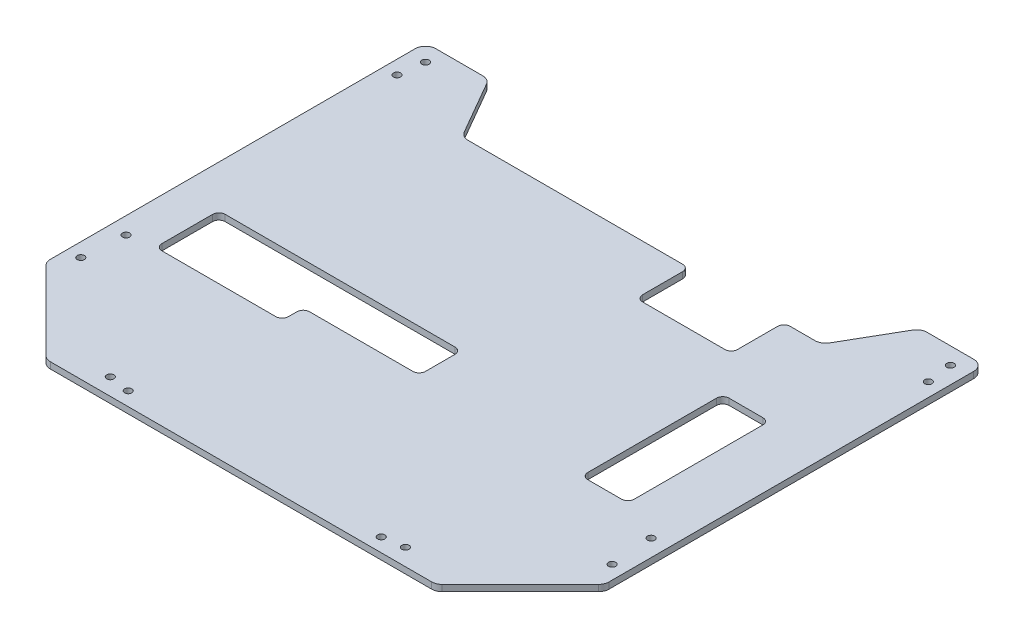
SolidWorks part; units mm, degrees
material "Acier non allié"
ref_plane "Front" through (0, 0, 0) normal (0, 0, 1) x (1, 0, 0)
ref_plane "Top" through (0, 0, 0) normal (0, 1, 0) x (1, 0, 0)
ref_plane "Right" through (0, 0, 0) normal (1, 0, 0) x (0, 0, -1)
sketch "Esquisse1" plane through (0, 0, 0) normal (0, 1, 0) x (1, 0, 0)
  line L0 (0, 0) -> (0, 1919.0564) construction
  line L1 (-92.5, 0) -> (92.5, 0)
  line L2 (92.5, 0) -> (132.5, 40)
  line L3 (132.5, 40) -> (132.5, 220)
  line L4 (132.5, 220) -> (102.5, 220)
  line L5 (102.5, 220) -> (85.1795, 190)
  line L6 (85.1795, 190) -> (-85.1795, 190)
  line L7 (-102.5, 220) -> (-85.1795, 190)
  line L8 (-132.5, 220) -> (-102.5, 220)
  line L9 (-132.5, 40) -> (-132.5, 220)
  line L10 (-92.5, 0) -> (-132.5, 40)
  point P12 (0, 190)
  dimension "D1" = 132.5
  dimension "D2" = 220
  dimension "D3" = 30
  dimension "D4" = 30
  dimension "D5" = 40
  dimension "D6" = 40
  dimension "D7" = 60
extrude "Boss.-Extru.1" add sketch "Esquisse1" along normal blind 3
fillet "Congé1" radius 5 10 edges at (132.5, 1.5, -220) (102.5, 1.5, -220) (85.1795, 1.5, -190) (-85.1795, 1.5, -190) (-102.5, 1.5, -220) (-132.5, 1.5, -220) (-132.5, 1.5, -40) (-92.5, 1.5, 0) (92.5, 1.5, 0) (132.5, 1.5, -40)
sketch "Esquisse2" plane through (0, 0, 0) normal (0, -1, 0) x (1, 0, 0)
  line L0 (0, 0) -> (0, -330.9968) construction
  line L1 (-90.4289, 0) -> (90.4289, 0) construction
  line L2 (-105.3868, -220) -> (-127.5, -220) construction
  line L3 (-132.5, -215) -> (-132.5, -42.0711) construction
  line L4 (-90.4289, 0) -> (90.4289, 0) construction
  line L5 (132.5, -42.0711) -> (132.5, -215) construction
  line L6 (127.5, -220) -> (105.3868, -220) construction
  circle A0 centre (-70, -8) radius 1
  circle A1 centre (-124.5, -70) radius 1
  circle A2 centre (-124.5, -212) radius 1
  circle A3 centre (124.5, -212) radius 1
  circle A4 centre (124.5, -70) radius 1
  circle A5 centre (70, -8) radius 1
  circle A6 centre (126, -50) radius 1.5
  circle A7 centre (126, -200) radius 1.5
  circle A8 centre (-60, -6.5) radius 1.5
  circle A9 centre (60, -6.5) radius 1.5
  circle A10 centre (-126, -50) radius 1.5
  circle A11 centre (-126, -200) radius 1.5
  dimension "D3" = 2
  dimension "D6" = 2
  dimension "D9" = 2
  dimension "D12" = 3
  dimension "D15" = 3
  dimension "D16" = 3
  dimension "D17" = 3
  dimension "D24" = 3
  dimension "D27" = 3
  dimension "D1" = 70
  dimension "D2" = 8
  dimension "D4" = 124.5
  dimension "D5" = 70
  dimension "D7" = 8
  dimension "D8" = 8
  dimension "D10" = 50
  dimension "D11" = 6.5
  dimension "D13" = 20
  dimension "D14" = 6.5
  dimension "D18" = 10
  dimension "D19" = 6.5
  dimension "D20" = 6.5
  dimension "D21" = 10
  dimension "D22" = 50
  dimension "D23" = 6.5
  dimension "D25" = 20
  dimension "D26" = 6.5
extrude "Enlèv. mat.-Extru.1" cut sketch "Esquisse2" against normal through all
hole_wizard "Dégagement M31" positions "Esquisse3" profile "Esquisse4" hole size "M3" standard "ISO" end condition through all
sketch "Esquisse3" plane through (0, 0, 0) normal (0, -1, 0) x (-1, 0, 0)
  point P0 (-70, 8)
  point P3 (-124.5, 70)
  point P6 (-124.5, 212)
  point P9 (124.5, 212)
  point P12 (124.5, 70)
  point P15 (70, 8)
  point P18 (-126, 200)
  point P21 (-126, 50)
  point P24 (-60, 6.5)
  point P27 (60, 6.5)
  point P41 (126, 200)
  point P44 (126, 50)
sketch "Esquisse4" plane through (70, 0, -8) normal (1, 0, 0) x (0, 0, -1)
  line L0 (0, 0) -> (0, 3)
  line L1 (0, 3) -> (1.7, 3)
  line L2 (1.7, 3) -> (1.7, 0)
  line L5 (1.7, 0) -> (0, 0)
  line L11 (0, -6.35) -> (0, 107.95) construction
  dimension "Diamètre du perçage jusqu'au prochain" = 3.4
  dimension "Profondeur du perçage jusqu'au prochain" = 3
sketch "Esquisse5" plane through (0, 0, 0) normal (0, -1, 0) x (1, 0, 0)
  line L6 (82.2927, -190) -> (-82.2927, -190) construction
  line L7 (22.5, -190) -> (67.5, -190)
  line L20 (22.5, -190) -> (22.5, -165)
  line L21 (22.5, -165) -> (67.5, -165)
  line L22 (67.5, -190) -> (67.5, -165)
  line L23 (132.5, -42.0711) -> (132.5, -215) construction
  line L24 (-112.5, -82) -> (-112.5, -72)
  line L25 (-112.5, -102) -> (2.5, -102)
  line L26 (-112.5, -102) -> (-112.5, -82)
  line L27 (-52.5, -82) -> (2.5, -82)
  line L28 (2.5, -102) -> (2.5, -82)
  line L29 (-132.5, -215) -> (-132.5, -42.0711) construction
  line L30 (127.5, -220) -> (105.3868, -220) construction
  line L31 (82.5, -146) -> (104.5, -146)
  line L32 (82.5, -146) -> (82.5, -79)
  line L33 (82.5, -79) -> (104.5, -79)
  line L34 (104.5, -146) -> (104.5, -79)
  line L35 (-90.4289, 0) -> (90.4289, 0) construction
  line L36 (-112.5, -72) -> (-52.5, -72)
  line L37 (-52.5, -82) -> (-52.5, -72)
  dimension "D1" = 65
  dimension "D2" = 110
  dimension "D3" = 25
  dimension "D4" = 82
  dimension "D5" = 135
  dimension "D6" = 20
  dimension "D7" = 115
  dimension "D8" = 50
  dimension "D9" = 74
  dimension "D10" = 67
  dimension "D11" = 22
  dimension "D15" = 30
  dimension "D16" = 60
extrude "Enlèv. mat.-Extru.2" cut sketch "Esquisse5" against normal through all
fillet "Congé2" radius 3 14 edges at (67.5, 1.5, -190) (67.5, 1.5, -165) (22.5, 1.5, -165) (22.5, 1.5, -190) (104.5, 1.5, -146) (82.5, 1.5, -146) (82.5, 1.5, -79) (104.5, 1.5, -79) (2.5, 1.5, -82) (2.5, 1.5, -102) (-112.5, 1.5, -102) (-52.5, 1.5, -72) (-52.5, 1.5, -82) (-112.5, 1.5, -72)
equation "\"WIDTH\"= 300mm'Total width of the robot"
equation "\"LENGTH\"= 220mm'Total length of the robot"
equation "\"CUT_DEPTH\"= 45mm'Depth of the cut on the edges of the plate"
equation "\"Plate_th\"= 3mm'Thickness of the plate"
equation "\"D1\"= \"Plate_th\""
